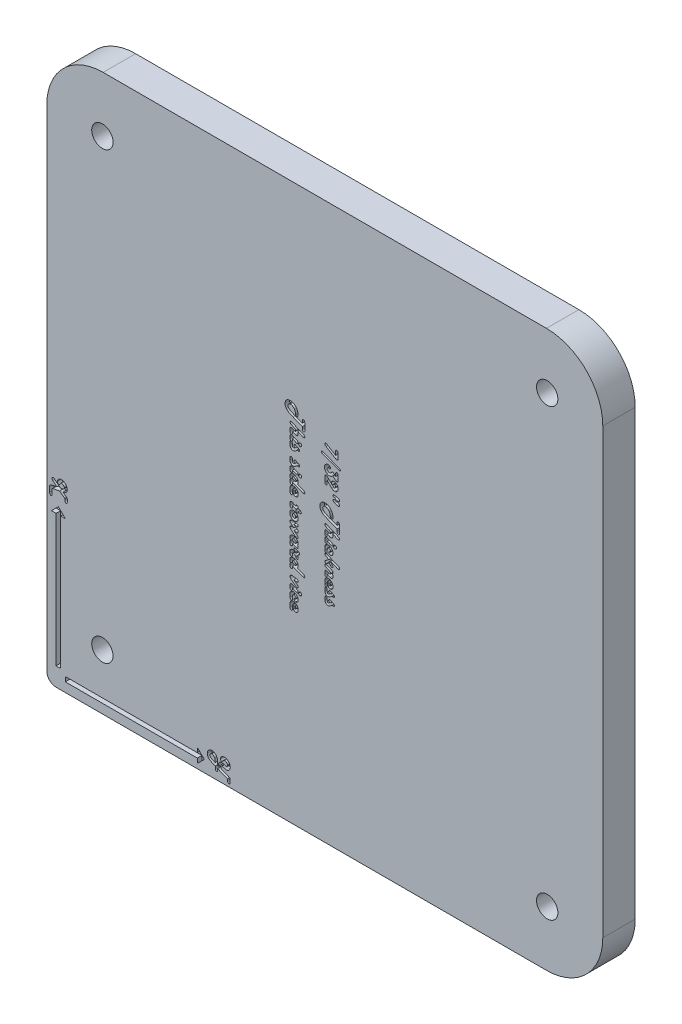
SolidWorks part; units mm, degrees
ref_plane "Front Plane" through (0, 0, 0) normal (0, 0, 1) x (1, 0, 0)
ref_plane "Top Plane" through (0, 0, 0) normal (0, 1, 0) x (1, 0, 0)
ref_plane "Right Plane" through (0, 0, 0) normal (1, 0, 0) x (0, 0, -1)
sketch "Sketch1" plane through (0, 0, 0) normal (0, 1, 0) x (1, 0, 0)
  line L7 (-50.8, -3.175) -> (50.8, -3.175)
  line L8 (-50.8, -3.175) -> (-50.8, 3.175)
  line L9 (-50.8, 3.175) -> (50.8, 3.175)
  line L10 (50.8, -3.175) -> (50.8, 3.175)
  line L11 (-50.8, -3.175) -> (50.8, 3.175) construction
  line L12 (-50.8, 3.175) -> (50.8, -3.175) construction
  point P4 (0, 0)
  point P14 (0, 0)
  dimension "Width" = 101.6
  dimension "Thickness" = 6.35
sketch "Sketch2" plane through (0, 0, 0) normal (0, 1, 0) x (0, 0, -1)
  line L0 (47.625, 50.8) -> (-53.975, 50.8) construction
  point P0 (73.025, 50.8)
  point P4 (-3.175, 50.8)
  point P6 (-79.375, 50.8)
  dimension "Length" = 101.6
  dimension "D1" = 127
  dimension "D2" = 127
sketch "Sketch3" plane through (0, 0, 0) normal (0, 1, 0) x (1, 0, 0)
  line L6 (-50.8, 3.175) -> (50.8, 3.175)
  line L7 (50.8, 3.175) -> (50.8, -3.175)
  line L8 (50.8, -3.175) -> (-50.8, -3.175)
  line L9 (-50.8, -3.175) -> (-50.8, 3.175)
extrude "Boss-Extrude1" add sketch "Sketch3" along normal mid plane 101.6
ref_plane "FacingBottom" through (0, 0, -2.7781) normal (0, 0, -1) x (1, 0, 0)
other "FacingBottomSurfaceCut"
ref_plane "FacingTop" through (0, 0, 2.7781) normal (0, 0, 1) x (-1, 0, 0)
other "FacingTopSurfaceCut"
sketch "BaseBorderRadiusSketch" plane through (0, 0, -2.7781) normal (0, 0, -1) x (1, 0, 0)
  line L12 (-47.625, 47.625) -> (-47.625, -47.625)
  line L13 (-47.625, -47.625) -> (47.625, -47.625)
  line L14 (47.625, -47.625) -> (47.625, 47.625)
  line L15 (47.625, 47.625) -> (-47.625, 47.625)
  line L16 (-47.625, 46.0375) -> (-47.625, -37.973)
  line L17 (-37.973, -47.625) -> (37.973, -47.625)
  line L18 (47.625, -37.973) -> (47.625, 37.973)
  line L19 (37.973, 47.625) -> (-46.0375, 47.625)
  arc A4 (-47.625, 46.0375) -> (-46.0375, 47.625) centre (-46.0375, 46.0375) cw
  arc A5 (-47.625, -37.973) -> (-37.973, -47.625) centre (-37.973, -37.973) ccw
  arc A6 (37.973, -47.625) -> (47.625, -37.973) centre (37.973, -37.973) ccw
  arc A7 (47.625, 37.973) -> (37.973, 47.625) centre (37.973, 37.973) ccw
  dimension "D2" = 1.5875
  dimension "D1" = 3.175
extrude "BaseBorderRadiusCut-Extrude" cut sketch "BaseBorderRadiusSketch" against normal through all flip side to cut
sketch "BumperInsetSketch" plane through (0, 0, -2.7781) normal (0, 0, 1) x (1, 0, 0)
  line L1 (-38.1, -38.1) -> (38.1, -38.1) construction
  line L2 (-38.1, -38.1) -> (-38.1, 38.1) construction
  line L3 (-38.1, 38.1) -> (38.1, 38.1) construction
  line L4 (38.1, -38.1) -> (38.1, 38.1) construction
  line L5 (-38.1, -38.1) -> (38.1, 38.1) construction
  line L6 (-38.1, 38.1) -> (38.1, -38.1) construction
  line L7 (47.625, 37.973) -> (47.625, -37.973) construction
  circle A0 centre (-38.1, 38.1) radius 3.175
  circle A1 centre (38.1, 38.1) radius 3.175
  circle A2 centre (38.1, -38.1) radius 3.175
  circle A3 centre (-38.1, -38.1) radius 3.175
  point P0 (0, 0)
  dimension "D2" = 6.35
  dimension "D1" = 9.525
hole_wizard "Bumper#6-32 Tapped Hole" positions "3DSketch4" profile "Sketch11" hole size "#27" standard "ANSI Inch" end condition through all
sketch3d "3DSketch4"
  point P0 (-38.1, 38.1, -2.7781)
sketch "Sketch11" plane through (-38.1, 38.1, -2.7781) normal (1, 0, 0) x (0, 1, 0)
  line L0 (0, 0) -> (0, 5.5562)
  line L1 (0, 5.5562) -> (1.8288, 5.5562)
  line L2 (1.8288, 5.5562) -> (1.8288, 0)
  line L5 (1.8288, 0) -> (0, 0)
  line L11 (0, -6.35) -> (0, 107.95) construction
  dimension "Thru Hole Dia." = 3.6576
  dimension "Thru Hole Depth" = 5.5562
pattern_linear "BumperThreadLPattern" count 2 spacing 76.2 along (0, -1, 0) count 2 spacing 76.2 along (1, 0, 0) of "Bumper#6-32 Tapped Hole"
extrude "BumperCuts" cut sketch "BumperInsetSketch" along normal blind 2.921
sketch "Sketch12" plane through (0, 0, 2.7781) normal (0, 0, 1) x (1, 0, 0)
  line L0 (-46.0375, -46.0375) -> (-17.4625, -46.0375) construction
  line L1 (-46.0375, -46.0375) -> (-46.0375, -17.4625) construction
  line L2 (-21.8281, -46.0375) -> (-21.8281, -46.8313)
  line L3 (-21.8281, -46.8313) -> (-20.6375, -45.6406)
  line L4 (-47.625, 37.973) -> (-47.625, -46.0375)
  line L5 (-46.0375, -47.625) -> (37.973, -47.625)
  line L6 (47.625, -37.973) -> (47.625, 37.973)
  line L7 (37.973, 47.625) -> (-37.973, 47.625)
  line L8 (-47.625, 37.973) -> (-47.625, -46.0375) construction
  line L9 (-46.0375, -47.625) -> (37.973, -47.625) construction
  line L10 (47.625, -37.973) -> (47.625, 37.973) construction
  line L11 (37.973, 47.625) -> (-37.973, 47.625) construction
  line L12 (-20.6375, -45.6406) -> (-21.8281, -44.45)
  line L13 (-21.8281, -44.45) -> (-21.8281, -45.2437)
  line L14 (-21.8281, -45.2437) -> (-44.45, -45.2437)
  line L15 (-45.2437, -44.45) -> (-45.2437, -21.8281)
  line L16 (-45.2437, -21.8281) -> (-44.45, -21.8281)
  line L17 (-44.45, -21.8281) -> (-45.6406, -20.6375)
  line L18 (-45.6406, -20.6375) -> (-46.8312, -21.8281)
  line L19 (-46.8312, -21.8281) -> (-46.0375, -21.8281)
  line L20 (-46.0375, -21.8281) -> (-46.0375, -44.45)
  line L21 (-44.45, -46.0375) -> (-21.8281, -46.0375)
  line L24 (-18.7625, -42.522) -> (-18.7625, -47.0739) construction
  line L25 (-46.0375, -44.45) -> (-45.2437, -44.45)
  line L26 (-44.45, -45.2437) -> (-44.45, -46.0375)
  line L27 (-46.6499, -14.9355) -> (-46.6499, -19.7392) construction
  line L28 (0, 14.9355) -> (0, -14.9355) construction
  arc A4 (-47.625, -46.0375) -> (-46.0375, -47.625) centre (-46.0375, -46.0375) ccw
  arc A5 (37.973, -47.625) -> (47.625, -37.973) centre (37.973, -37.973) ccw
  arc A6 (47.625, 37.973) -> (37.973, 47.625) centre (37.973, 37.973) ccw
  arc A7 (-37.973, 47.625) -> (-47.625, 37.973) centre (-37.973, 37.973) ccw
  arc A8 (-47.625, -46.0375) -> (-46.0375, -47.625) centre (-46.0375, -46.0375) ccw construction
  arc A9 (37.973, -47.625) -> (47.625, -37.973) centre (37.973, -37.973) ccw construction
  arc A10 (47.625, 37.973) -> (37.973, 47.625) centre (37.973, 37.973) ccw construction
  arc A11 (-37.973, 47.625) -> (-47.625, 37.973) centre (-37.973, 37.973) ccw construction
  text T0 "Y" font "Harlow Solid Italic" height in points 10
  text T1 "X\r\n" font "Harlow Solid Italic" height in points 10
  text T2 "7/32\" Thickness\r\nThis side toward vice" font "Harlow Solid Italic" height in points 10
  point P27 (0, 0)
  point P28 (-2.9379, 35.4994)
  point P31 (0, 0)
  point P36 (0, 0)
  point P48 (0, 0)
  dimension "D2" = 28.575
  dimension "D3" = 28.575
  dimension "D4" = 25.4
  dimension "D5" = 0.7937
  dimension "D6" = 0.7937
  dimension "D7" = 45
  dimension "D1" = 0
extrude "Cut-Extrude1" cut sketch "Sketch12" against normal blind 0.7937
sketch "Sketch13" plane through (0, 0, -2.7781) normal (0, 0, -1) x (-1, 0, 0)
  line L0 (42.6849, -18.125) -> (47.2943, -18.125) construction
  line L1 (15.0585, -45.4148) -> (18.1847, -45.4148) construction
  line L2 (-18.3637, 0) -> (18.3637, 0) construction
  line L18 (45.2437, -21.8281) -> (45.2437, -44.45)
  line L19 (44.45, -21.8281) -> (45.2437, -21.8281)
  line L20 (45.6406, -20.6375) -> (44.45, -21.8281)
  line L21 (46.8312, -21.8281) -> (45.6406, -20.6375)
  line L22 (46.0375, -21.8281) -> (46.8312, -21.8281)
  line L23 (46.0375, -44.45) -> (46.0375, -21.8281)
  line L30 (45.2437, -44.45) -> (46.0375, -44.45)
  line L31 (45.2437, -21.8281) -> (45.2437, -44.45)
  line L32 (44.45, -21.8281) -> (45.2437, -21.8281)
  line L33 (45.6406, -20.6375) -> (44.45, -21.8281)
  line L34 (46.8312, -21.8281) -> (45.6406, -20.6375)
  line L35 (46.0375, -21.8281) -> (46.8312, -21.8281)
  line L36 (46.0375, -44.45) -> (46.0375, -21.8281)
  line L37 (45.2437, -44.45) -> (46.0375, -44.45)
  line L38 (44.45, -45.2437) -> (21.8281, -45.2437)
  line L39 (21.8281, -45.2437) -> (21.8281, -44.45)
  line L40 (21.8281, -44.45) -> (20.6375, -45.6406)
  line L41 (20.6375, -45.6406) -> (21.8281, -46.8313)
  line L42 (21.8281, -46.8313) -> (21.8281, -46.0375)
  line L43 (21.8281, -46.0375) -> (44.45, -46.0375)
  line L44 (44.45, -46.0375) -> (44.45, -45.2437)
  line L45 (44.45, -45.2437) -> (21.8281, -45.2437)
  line L46 (21.8281, -45.2437) -> (21.8281, -44.45)
  line L47 (21.8281, -44.45) -> (20.6375, -45.6406)
  line L48 (20.6375, -45.6406) -> (21.8281, -46.8313)
  line L49 (21.8281, -46.8313) -> (21.8281, -46.0375)
  line L50 (21.8281, -46.0375) -> (44.45, -46.0375)
  line L51 (44.45, -46.0375) -> (44.45, -45.2437)
  spline S0 degree 3 poles (18.1847, -45.4148) (18.1925, -45.3985) (18.2081, -45.3659) (18.2231, -45.3134) (18.2329, -45.2587) (18.2341, -45.2211) (18.2347, -45.202) knots 0 0 0 0 0.24549 0.489965 0.740342 1 1 1 1 construction
  text T0 "Y" font "Harlow Solid Italic" height in points 10
  text T1 "X" font "Harlow Solid Italic" height in points 10
  text T2 "~3/32\" Thickness\r\nThis side toward vice" font "Harlow Solid Italic" height in points 10
  point P12 (44.9896, -18.125)
  point P24 (0, 0)
  point P26 (41.7978, -18.1148)
  point P27 (15.0585, -45.6732)
  point P28 (0, 0)
  point P29 (19.4773, -46.0375)
  point P32 (0, 0)
  point P33 (42.6849, -18.125)
  dimension "D1" = 0
  dimension "D2" = 0
extrude "Cut-Extrude3" cut sketch "Sketch13" against normal blind 0.7937
equation "\"D1@Boss-Extrude1\" = \"Length@Sketch2\""
equation "\"D1@Sketch2\"=\"Width@Sketch1\" * 1.25"
equation "\"D2@Sketch2\"=\"D1@Sketch2\""
